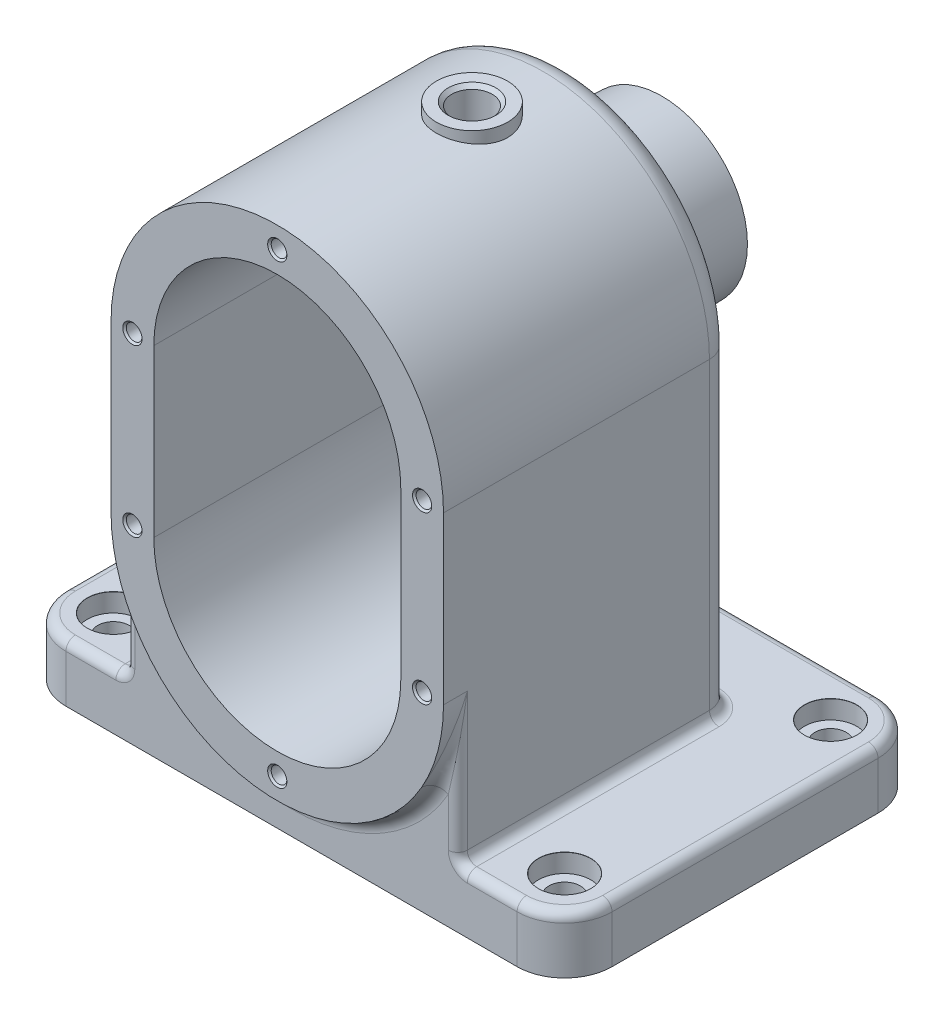
SolidWorks part; units mm, degrees
ref_plane "Front Plane" through (0, 0, 0) normal (0, 0, 1) x (1, 0, 0)
ref_plane "Top Plane" through (0, 0, 0) normal (0, 1, 0) x (1, 0, 0)
ref_plane "Right Plane" through (0, 0, 0) normal (1, 0, 0) x (0, 0, -1)
sketch "Sketch1" plane through (0, 0, 0) normal (0, 0, 1) x (1, 0, 0)
  line L0 (0, -17.5) -> (0, 17.5) construction
  line L1 (-35, -17.5) -> (-35, 17.5)
  line L2 (35, -17.5) -> (35, 17.5)
  arc A0 (-35, -17.5) -> (35, -17.5) centre (0, -17.5) ccw
  arc A1 (35, 17.5) -> (-35, 17.5) centre (0, 17.5) ccw
  point P2 (0, 0)
  dimension "D1" = 35
  dimension "D2" = 35
extrude "Boss-Extrude1" add sketch "Sketch1" along normal mid plane 58
shell "Shell1" thickness 9 removed face at (0, 0, 29)
sketch "Sketch2" plane through (0, 0, 0) normal (1, 0, 0) x (0, 0, -1)
  line L0 (29, 17.5) -> (49, 17.5)
  line L1 (29, 17.5) -> (29, -1.2791)
  line L2 (29, -17.5) -> (29, 17.5) construction
  line L4 (49, 17.5) -> (49, -0.5)
  line L5 (49, -0.5) -> (29, -1.2791)
  dimension "D1" = 18
  dimension "D2" = 20
revolve "Revolve1" add sketch "Sketch2" angle 360 about L0
sketch "Sketch4" plane through (0, 0, 0) normal (1, 0, 0) x (0, 0, -1)
  line L0 (20, 17.5) -> (5, 17.5)
  line L1 (-29, 17.5) -> (29, 17.5) construction
  line L2 (5, 17.5) -> (5, 35.5)
  line L4 (20, 34.3026) -> (20, 17.5)
  line L5 (29, 17.5) -> (29, 52.5) construction
  line L6 (5, 35.5) -> (72.4543, 35.5) construction
  line L7 (5, 35.5) -> (20, 36.5489)
  line L8 (20, 36.5489) -> (20, 34.3026)
  dimension "D1" = 9
  dimension "D2" = 15
  dimension "D3" = 18
  dimension "D4" = 4
revolve "Revolve2" add sketch "Sketch4" angle 360 about L0
sketch "Sketch6" plane through (0, 0, 0) normal (1, 0, 0) x (0, 0, -1)
  line L7 (20, -17.5) -> (20, -8.5139)
  line L17 (-29, -17.5) -> (29, -17.5) construction
  line L20 (20, -17.5) -> (5, -17.5)
  line L21 (5, -17.5) -> (5, -8)
  line L22 (5, -8) -> (20, -6.9511)
  line L23 (20, -6.9511) -> (20, -8.5139)
  line L24 (5, -8) -> (40.9192, -8) construction
  line L25 (-29, 17.5) -> (29, 17.5) construction
  dimension "D1" = 9
  dimension "D2" = 4
  dimension "D3" = 15
  dimension "D4" = 9.5
  dimension "D5" = 10.5489
  dimension "D6" = 35
revolve "Revolve3" add sketch "Sketch6" angle 360 about L20
sketch "Sketch7" plane through (0, 0, -49) normal (0, 0, -1) x (-1, 0, 0)
  circle A0 centre (0, 17.5) radius 14
  dimension "D1" = 28
extrude "Cut-Extrude1" cut sketch "Sketch7" against normal blind 15
sketch "Sketch8" plane through (0, 0, -34) normal (0, 0, -1) x (-1, 0, 0)
  circle A0 centre (0, 17.5) radius 10.5
  dimension "D1" = 21
extrude "Cut-Extrude2" cut sketch "Sketch8" against normal blind 14.8
sketch "Sketch9" plane through (0, 0, -19.2) normal (0, 0, -1) x (-1, 0, 0)
  circle A0 centre (0, 17.5) radius 9
  dimension "D1" = 18
extrude "Boss-Extrude2" add sketch "Sketch9" against normal blind 14.8
sketch "Sketch10" plane through (0, 0, 0) normal (0, 0, 1) x (1, 0, 0)
  circle A0 centre (0, 17.5) radius 10.5
  dimension "D1" = 21
extrude "Cut-Extrude3" cut sketch "Sketch10" against normal blind 5
sketch "Sketch11" plane through (0, 0, -19.2) normal (0, 0, -1) x (-1, 0, 0)
  circle A0 centre (0, 17.5) radius 11
  dimension "D1" = 22
extrude "Cut-Extrude4" cut sketch "Sketch11" against normal blind 1.1
sketch "Sketch12" plane through (0, 0, -5) normal (0, 0, 1) x (1, 0, 0)
  circle A0 centre (0, 17.5) radius 10.5
  dimension "D1" = 21
extrude "Cut-Extrude5" cut sketch "Sketch12" against normal through all
sketch "Sketch13" plane through (0, 0, -5) normal (0, 0, 1) x (1, 0, 0)
  circle A0 centre (0, -17.5) radius 6
  dimension "D1" = 12
extrude "Cut-Extrude6" cut sketch "Sketch13" against normal through all both and the other way through all
sketch "Sketch16" plane through (0, 0, 29) normal (0, 0, 1) x (1, 0, 0)
  line L0 (35, -17.5) -> (35, 17.5) construction
  line L1 (-35, 17.5) -> (-35, -17.5) construction
  line L2 (26, -17.5) -> (26, 17.5) construction
  line L3 (-26, 17.5) -> (-26, -17.5) construction
  line L4 (35, -17.5) -> (35, 17.5)
  line L5 (-35, 17.5) -> (-35, -17.5)
  line L6 (26, -17.5) -> (26, 17.5)
  line L7 (-26, 17.5) -> (-26, -17.5)
  arc A0 (-35, -17.5) -> (35, -17.5) centre (0, -17.5) ccw construction
  arc A1 (35, 17.5) -> (-35, 17.5) centre (0, 17.5) ccw construction
  arc A2 (-26, -17.5) -> (26, -17.5) centre (0, -17.5) ccw construction
  arc A3 (26, 17.5) -> (-26, 17.5) centre (0, 17.5) ccw construction
  arc A4 (-35, -17.5) -> (35, -17.5) centre (0, -17.5) ccw
  arc A5 (35, 17.5) -> (-35, 17.5) centre (0, 17.5) ccw
  arc A6 (-26, -17.5) -> (26, -17.5) centre (0, -17.5) ccw
  arc A7 (26, 17.5) -> (-26, 17.5) centre (0, 17.5) ccw
extrude "Boss-Extrude4" add sketch "Sketch16" along normal blind 3
sketch "Sketch18" plane through (0, 0, 0) normal (1, 0, 0) x (0, 0, -1)
  line L1 (-29, -48.5) -> (47, -48.5)
  line L2 (-29, -48.5) -> (-29, -60.5)
  line L3 (-29, -60.5) -> (47, -60.5)
  line L4 (47, -48.5) -> (47, -60.5)
  dimension "D1" = 3
  dimension "D2" = 76
  dimension "D3" = 12
  dimension "D4" = 66
extrude "Boss-Extrude5" add sketch "Sketch18" along normal mid plane 115
sketch "Sketch19" plane through (0, 0, -29) normal (0, 0, -1) x (-1, 0, 0)
  line L0 (-57.5, -48.5) -> (57.5, -48.5) construction
  line L1 (-35, -48.5) -> (-16.2481, -48.5)
  line L2 (-35, -17.5) -> (-35, -48.5)
  line L3 (35, -17.5) -> (35, -48.5)
  line L4 (16.2481, -48.5) -> (35, -48.5)
  arc A0 (-35, -17.5) -> (-16.2481, -48.5) centre (0, -17.5) ccw construction
  arc A1 (-35, -17.5) -> (-16.2481, -48.5) centre (0, -17.5) ccw
  arc A2 (16.2481, -48.5) -> (35, -17.5) centre (0, -17.5) ccw construction
  arc A3 (16.2481, -48.5) -> (35, -17.5) centre (0, -17.5) ccw
  arc M4 (16.2481, -48.5) -> (35, -17.5) centre (0, -17.5) ccw
  arc M8 (-35, -17.5) -> (-16.2481, -48.5) centre (0, -17.5) ccw
extrude "Boss-Extrude6" add sketch "Sketch19" against normal up to surface (58 mm away) contours L2 L1 M8 | L3 L1 M4 region at (29.7786, -41.2241, -29) region at (-29.7786, -41.2241, -29) up to face at (0, -53.1667, 29)
sketch "Sketch21" plane through (0, 0, 0) normal (0, 0, 1) x (1, 0, 0)
sketch "Sketch22" plane through (0, 0, -29) normal (0, 0, -1) x (-1, 0, 0)
  circle A0 centre (0, -17.5) radius 7.5
  circle A1 centre (0, -17.5) radius 6 construction
  circle A2 centre (0, -17.5) radius 6
  dimension "D1" = 15
extrude "Boss-Extrude8" add sketch "Sketch22" along normal blind 2
fillet "Fillet1" radius 10 4 edges at (-57.5, -54.5, -47) (57.5, -54.5, -47) (-57.5, -54.5, 29) (57.5, -54.5, 29)
hole_wizard "CBORE for M6 Cheese Head Screw1" positions "Sketch24" profile "Sketch25" counterbore size "M6" standard "ISO" end condition through all
sketch "Sketch24" plane through (0, -48.5, 0) normal (0, 1, 0) x (1, 0, 0)
  point P0 (-47.5, -19)
sketch "Sketch25" plane through (-47.5, -48.5, 19) normal (1, 0, 0) x (0, 0, 1)
  line L0 (0, 0) -> (0, 12)
  line L1 (0, 12) -> (3.3, 12)
  line L3 (3.3, 12) -> (3.3, 3.9)
  line L4 (5.5, 3.9) -> (3.3, 3.9)
  line L5 (5.5, 3.9) -> (5.5, 0.025)
  line L6 (5.5, 0.025) -> (5.525, 0)
  line L7 (5.525, 0) -> (0, 0)
  line L8 (-5.5, 0.025) -> (-5.525, 0) construction
  line L11 (0, -6.35) -> (0, 107.95) construction
  dimension "Thru Hole Dia." = 6.6
  dimension "Thru Hole Depth" = 12
  dimension "C'Bore Dia." = 11
  dimension "C'Bore Depth" = 3.9
  dimension "Near C'Sink Dia." = 11.05
  dimension "Near C'Sink Angle" = 90
hole_wizard "CBORE for M6 Cheese Head Screw2" positions "3DSketch1" profile "Sketch26" counterbore size "M6" standard "ISO" end condition through all
sketch3d "3DSketch1"
  line L0 (-47.5, -60.5, -37) -> (-47.5, -48.5, -37) construction
  line L1 (47.5, -48.5, -37) -> (47.5, -60.5, -37) construction
  line L2 (47.5, -60.5, 19) -> (47.5, -48.5, 19) construction
  point P0 (-47.5, -48.5, -37)
  point P4 (47.5, -48.5, -37)
  point P8 (47.5, -48.5, 19)
sketch "Sketch26" plane through (-47.5, -48.5, -37) normal (1, 0, 0) x (0, 0, 1)
  line L0 (0, 0) -> (0, 12)
  line L1 (0, 12) -> (3.3, 12)
  line L3 (3.3, 12) -> (3.3, 3.9)
  line L4 (5.5, 3.9) -> (3.3, 3.9)
  line L5 (5.5, 3.9) -> (5.5, 0.025)
  line L6 (5.5, 0.025) -> (5.525, 0)
  line L7 (5.525, 0) -> (0, 0)
  line L8 (-5.5, 0.025) -> (-5.525, 0) construction
  line L11 (0, -6.35) -> (0, 107.95) construction
  dimension "Thru Hole Dia." = 6.6
  dimension "Thru Hole Depth" = 12
  dimension "C'Bore Dia." = 11
  dimension "C'Bore Depth" = 3.9
  dimension "Near C'Sink Dia." = 11.05
  dimension "Near C'Sink Angle" = 90
fillet "Fillet2" radius 5 3 edges at (35, -15.5, -29) (-35, -15.5, -29) (0, 52.5, -29)
fillet "Fillet3" radius 2 19 edges at (35, -33, 29) (-35, -33, 29) (41.25, -48.5, 29) (54.5711, -48.5, 26.0711) (57.5, -48.5, -9) (54.5711, -48.5, -44.0711) (-41.25, -48.5, 29) (-54.5711, -48.5, 26.0711) (-57.5, -48.5, -9) (-54.5711, -48.5, -44.0711) (-35, -48.5, 2.5) (-33.5355, -48.5, -27.5355) (35, -48.5, 2.5) (33.5355, -48.5, -27.5355) (10.5489, -17.5, -20) (7.5, -17.5, -29) (0, -48.5, -47) (18.7791, 17.5, -29) (0, -48.5, -29)
sketch "Sketch27" plane through (0, 0, 32) normal (0, 0, 1) x (1, 0, 0)
  point P35 (0, 48)
  point P36 (-30.5, 17.5)
  point P37 (-30.5, -17.5)
  point P38 (0, -48)
  point P39 (30.5, -17.5)
  point P40 (30.5, 17.5)
hole_wizard "M4 Tapped Hole1" positions "3DSketch2" profile "Sketch28" tap size "M4" standard "ISO"
sketch3d "3DSketch2"
  point P0 (0, 48, 32)
  point P3 (-30.5, 17.5, 32)
  point P6 (-30.5, -17.5, 32)
  point P9 (0, -48, 32)
  point P12 (30.5, -17.5, 32)
  point P15 (30.5, 17.5, 32)
sketch "Sketch28" plane through (0, 48, 32) normal (1, 0, 0) x (0, -1, 0)
  line L0 (0, 0) -> (0, 13.9914)
  line L1 (0, 13.9914) -> (1.65, 13)
  line L2 (1.65, 13) -> (1.65, 0.375)
  line L3 (1.65, 0.375) -> (2.025, 0)
  line L5 (2.025, 0) -> (0, 0)
  line L6 (-1.65, 0.375) -> (-2.025, 0) construction
  line L10 (0, 13.9914) -> (-1.65, 13) construction
  line L11 (0, -6.35) -> (0, 107.95) construction
  dimension "Tap Drill Dia." = 3.3
  dimension "Tap Drill Depth" = 13
  dimension "Near C'Sink Dia." = 4.05
  dimension "Near C'Sink Angle" = 90
  dimension "Drill Angle" = 118
cosmetic thread "Hole Thread1" parameters "D1"=10, "D2"=4
cosmetic thread "Hole Thread2" parameters "D1"=10, "D2"=4
cosmetic thread "Hole Thread3" parameters "D1"=10, "D2"=4
cosmetic thread "Hole Thread4" parameters "D1"=10, "D2"=4
cosmetic thread "Hole Thread5" parameters "D1"=10, "D2"=4
cosmetic thread "Hole Thread6" parameters "D1"=10, "D2"=4
fillet "Fillet4" radius 3 3 edges at (34.1166, -25.3141, 28.6593) (-34.1166, -25.3141, 28.6593) (0, -52.5, 29)
ref_plane "Plane1" through (0, 52.5, 0) normal (0, 1, 0) x (1, 0, 0)
sketch "Sketch29" plane through (0, 52.5, 0) normal (0, 1, 0) x (1, 0, 0)
  circle A0 centre (0, 9) radius 7.5
  dimension "D2" = 15
extrude "Boss-Extrude9" add sketch "Sketch29" along normal blind 2 and the other way up to surface other way up to face at (0, 35, 4)
hole_wizard "M10 Tapped Hole1" positions "3DSketch3" profile "Sketch31" tap size "M10" standard "ISO" end condition up to next
sketch3d "3DSketch3"
  line L0 (0, 54.5, -9) -> (0, 52.5, -9) construction
  point P0 (0, 54.5, -9)
sketch "Sketch31" plane through (0, 54.5, -9) normal (1, 0, 0) x (0, 0, 1)
  line L0 (0, 0) -> (0, 11)
  line L1 (0, 11) -> (4.25, 11)
  line L2 (4.25, 11) -> (4.25, 0.775)
  line L3 (4.25, 0.775) -> (5.025, 0)
  line L5 (5.025, 0) -> (0, 0)
  line L6 (-4.25, 0.775) -> (-5.025, 0) construction
  line L11 (0, -6.35) -> (0, 107.95) construction
  dimension "Thru Tap Drill Dia." = 8.5
  dimension "Thru Tap Drill Depth" = 11
  dimension "Near C'Sink Dia." = 10.05
  dimension "Near C'Sink Angle" = 90
cosmetic thread "Hole Thread7" parameters "D2"=10
